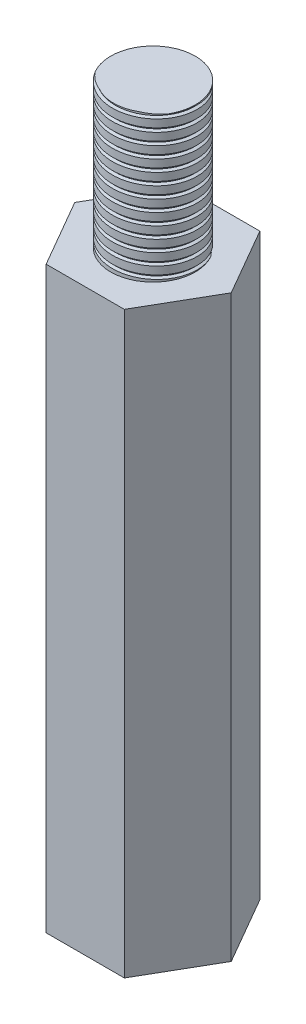
SolidWorks part; units mm, degrees
note: The reader was unsure of these and kept them because the rebuilt part matched: shared geometry of "草图1<3>".
ref_plane "前视基准面" through (0, 0, 0) normal (0, 0, 1) x (1, 0, 0)
ref_plane "上视基准面" through (0, 0, 0) normal (0, 1, 0) x (1, 0, 0)
ref_plane "右视基准面" through (0, 0, 0) normal (1, 0, 0) x (0, 0, -1)
sketch "草图1" plane through (0, 0, 0) normal (0, 1, 0) x (1, 0, 0)
  line L0 (0, 0) -> (0, 4.5761) construction
  line L1 (1.351, -2.34) -> (2.702, 0)
  line L2 (2.702, 0) -> (1.351, 2.34)
  line L3 (1.351, 2.34) -> (-1.351, 2.34)
  line L4 (-1.351, 2.34) -> (-2.702, 0)
  line L5 (-2.702, 0) -> (-1.351, -2.34)
  line L6 (-1.351, -2.34) -> (1.351, -2.34)
  line L7 (0, 4.5761) -> (0, -3.6794) construction
  circle A0 centre (0, 0) radius 2.34 construction
  circle A1 centre (0, 0) radius 1.46
  dimension "D1" = 4.68
  dimension "D2" = 2.92
extrude "凸台-拉伸1" add sketch "草图1" along normal blind 20 contours A1 | L5 L6 L1 L2 L3 L4 A1
extrude "切除-拉伸1" cut sketch "草图1<3>" along normal blind 5 contours A1
sketch "草图1<3>" plane through (0, 0, 0) normal (0, 1, 0) x (1, 0, 0) same geometry as "草图1"
sketch "草图2" plane through (0, 20, 0) normal (0, 1, 0) x (1, 0, 0)
  circle A0 centre (0, 0) radius 1.46
  dimension "D1" = 2.92
extrude "凸台-拉伸2" add sketch "草图2" along normal blind 5 separate body
ref_plane "基准面1" through (0, 0, 0) normal (0, 0, -1) x (-1, 0, 0)
sketch "草图4" plane through (0, 0, 0) normal (0, 0, -1) x (-1, 0, 0)
  line L0 (0, 0) -> (0, 28.5702) construction
  line L1 (-1.56, 20) -> (-1.56, 20.2)
  line L2 (-1.56, 20.2) -> (-1.36, 20.1333)
  line L3 (-1.36, 20.0667) -> (-1.56, 20)
  line L4 (-1.26, 20.1) -> (-2.0659, 20.1) construction
  line L5 (-2.0659, 20.1) -> (-0.8933, 20.1) construction
  line L7 (-1.46, 25) -> (-1.46, 20) construction
  line L8 (-1.36, 20.1333) -> (-1.36, 20.0667)
  line L9 (-1.46, 20) -> (1.46, 20) construction
  point P14 (0, 0)
  point P15 (0, 0)
  dimension "D1" = 0.1
  dimension "D2" = 0.1
  dimension "D3" = 0.1
  dimension "D4" = 0.3
  dimension "D5" = 0.2
  dimension "D6" = 0.1
  dimension "D7" = 0.0667
  dimension "D8" = 0.0667
ref_plane "基准面2" through (0, 20.1, 0) normal (0, 1, 0) x (1, 0, 0)
sketch "草图5" plane through (0, 20.1, 0) normal (0, 1, 0) x (1, 0, 0)
  circle A0 centre (0, 0) radius 1.46
  dimension "D1" = 2.92
curve "螺旋线/涡状线1" pitch 0.4 height 7.5 turns 18.75
sweep "切除-扫描1" cut profiles "草图4" path "螺旋线/涡状线1"
sketch "草图6" plane through (0, 0, 0) normal (0, -1, 0) x (1, 0, 0)
  circle A0 centre (0, 0) radius 1.46
curve "螺旋线/涡状线2" pitch 0.4 height 9.5 turns 23.75
sketch "草图7" plane through (0, 0, 0) normal (0, 0, -1) x (-1, 0, 0)
  line L0 (1.46, 0.2) -> (1.66, 0.1333)
  line L1 (1.66, 0.0667) -> (1.46, 0)
  line L2 (1.46, 0.2) -> (1.46, 0)
  line L3 (1.66, 0.1333) -> (1.66, 0.0667)
  line L8 (1.351, 0) -> (-1.351, 0) construction
  dimension "D1" = 0.2
  dimension "D3" = 1.46
  dimension "D4" = 0.2
sweep "切除-扫描2" cut profiles "草图7" path "螺旋线/涡状线2"
equation "\"chang\"= 20mm"
equation "\"r\"= 2.92mm"
equation "\"luowengao\"= 6.5mm"
equation "\"rr\"= 4.68mm"
equation "\"D1@草图1\"=\"rr\""
equation "\"D2@草图1\"=\"r\""
equation "\"D1@凸台-拉伸1\"=\"chang\""
equation "\"D1@切除-拉伸1\"=\"luowengao\"+5mm"
equation "\"D1@草图2\"=\"r\""
equation "\"D1@凸台-拉伸2\"=\"luowengao\""
